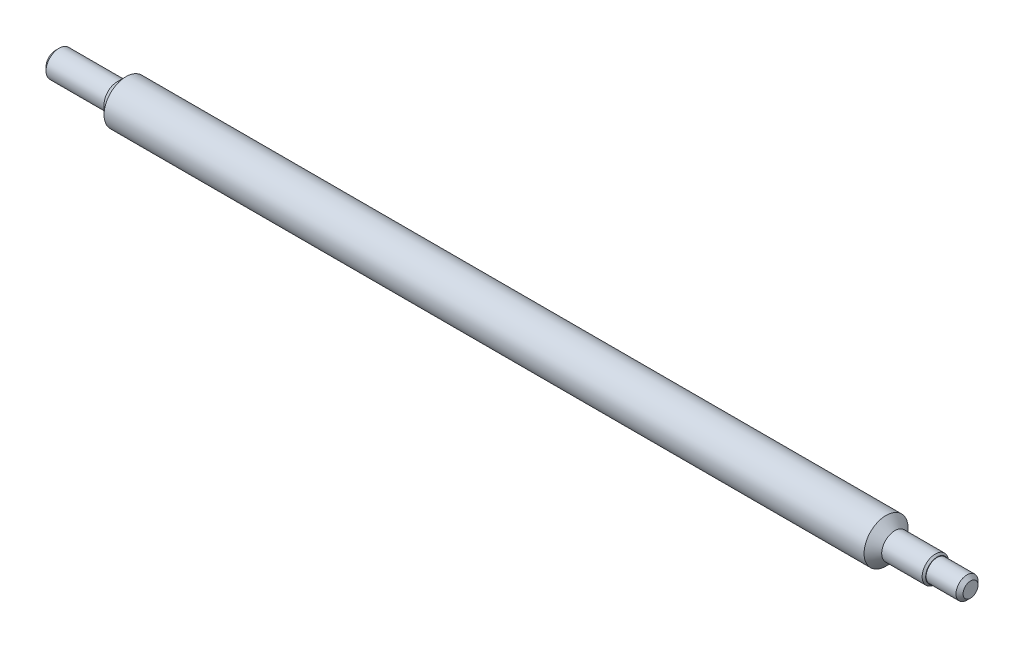
SolidWorks part; units mm, degrees
ref_plane "Спереди" through (0, 0, 0) normal (0, 0, 1) x (1, 0, 0)
ref_plane "Сверху" through (0, 0, 0) normal (0, 1, 0) x (1, 0, 0)
ref_plane "Справа" through (0, 0, 0) normal (1, 0, 0) x (0, 0, -1)
sketch "Эскиз1" plane through (0, 0, 0) normal (1, 0, 0) x (0, 0, -1)
  circle A0 centre (0, 0) radius 2.5
  dimension "D1" = 5
extrude "Бобышка-Вытянуть1" add sketch "Эскиз1" along normal blind 100
cosmetic thread "Условное изображение резьбы1" parameters "D2"=4
sketch "Эскиз3" plane through (100, 0, 0) normal (1, 0, 0) x (0, 0, -1)
  circle A0 centre (0, 0) radius 2.5
curve "Спираль1" pitch 1 height 100 turns 100
sketch "Эскиз13" plane through (0, 0, 0) normal (0, 1, 0) x (1, 0, 0)
  line L0 (0, -1.5) -> (3, -1.5)
  line L1 (3, -1.5) -> (4, -2.5)
  line L2 (4, -2.5) -> (0, -2.5)
  line L3 (0, -2.5) -> (0, -1.5)
  line L5 (0, 0) -> (0, -1.5) construction
  line L7 (0, 0) -> (2.812, 0) construction
  dimension "D1" = 3
  dimension "D2" = 1.5
  dimension "D3" = 2.5
  dimension "D4" = 45
revolve "Вырез-Повернуть1" cut sketch "Эскиз13" angle 360 about L7 region at (1.7619, 0, 2.0238)
sketch "Эскиз14" plane through (0, 0, 0) normal (0, 0, 1) x (1, 0, 0)
  line L2 (100, 1.5) -> (91.4, 1.5)
  line L3 (91.4, 1.5) -> (90.4, 2.5)
  line L4 (90.4, 2.5) -> (100, 2.5)
  line L6 (100, 0) -> (94.9951, 0) construction
  line L7 (100, 2.5) -> (100, 1.5)
  line L8 (100, -2.5) -> (100, 2.5) construction
  dimension "D1" = 1.5
  dimension "D2" = 2.5
  dimension "D3" = 9.6
  dimension "D4" = 45
revolve "Вырез-Повернуть9" cut sketch "Эскиз14" angle 360 about L6
sketch "Эскиз15" plane through (100, 0, 0) normal (1, 0, 0) x (0, 0, -1)
  circle A0 centre (0, 0) radius 1.25
  circle A1 centre (0, 0) radius 1.5 construction
  circle A2 centre (0, 0) radius 1.5
  dimension "D1" = 2.5
extrude "Вырез-Вытянуть1" cut sketch "Эскиз15" against normal blind 3.8
chamfer "Фаска2" distance 0.2 angle 45 1 edges at (96.2, 0, -1.5)
chamfer "Фаска3" distance 0.4 angle 45 1 edges at (100, 0, -1.25)
sketch "Эскиз16" plane through (0, 0, 0) normal (-1, 0, 0) x (0, 0, 1)
  circle A1 centre (0, 0) radius 1.5
  circle A2 centre (0, 0) radius 1.5
  dimension "D1" = 0
extrude "Бобышка-Вытянуть2" add sketch "Эскиз16" along normal blind 4
chamfer "Фаска4" distance 0.4 angle 45 1 edges at (-4, 0, 1.5)
